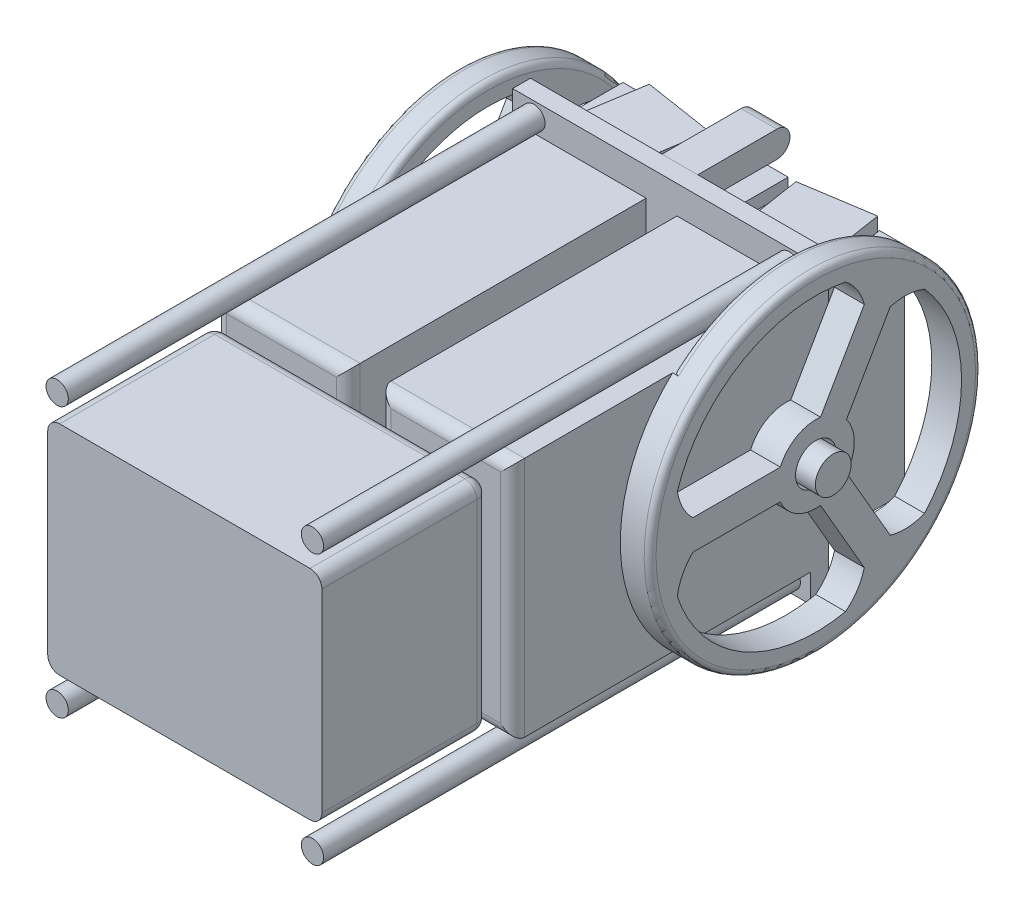
SolidWorks part; units mm, degrees
ref_plane "前视基准面" through (0, 0, 0) normal (0, 0, 1) x (1, 0, 0)
ref_plane "上视基准面" through (0, 0, 0) normal (0, 1, 0) x (1, 0, 0)
ref_plane "右视基准面" through (0, 0, 0) normal (1, 0, 0) x (0, 0, -1)
sketch "草图1" plane through (0, 0, 0) normal (0, 0, 1) x (1, 0, 0)
  line L1 (25, -25) -> (-25, -25)
  line L2 (25, -25) -> (25, 25)
  line L3 (25, 25) -> (-25, 25)
  line L4 (-25, -25) -> (-25, 25)
  line L5 (25, -25) -> (-25, 25) construction
  line L6 (25, 25) -> (-25, -25) construction
  point P0 (0, 0)
  dimension "D1" = 50
  dimension "D2" = 50
extrude "凸台-拉伸2" add sketch "草图1" along normal blind 3
sketch "草图3" plane through (0, 0, 3) normal (0, 0, 1) x (1, 0, 0)
  line L0 (-25, 25) -> (-25, -25) construction
  line L1 (-2.5874, 20.2707) -> (-25, 20.2707)
  line L2 (-2.5874, 20.2707) -> (-2.5874, -20.2707)
  line L3 (-2.5874, -20.2707) -> (-25, -20.2707)
  line L4 (-25, 20.2707) -> (-25, -20.2707)
  line L8 (2.5874, -20.2707) -> (25, -20.2707)
  line L9 (25, 20.2707) -> (25, -20.2707)
  line L10 (2.5874, 20.2707) -> (25, 20.2707)
  line L11 (2.5874, 20.2707) -> (2.5874, -20.2707)
  point P0 (-13.7937, 0)
extrude "凸台-拉伸10" add sketch "草图3" along normal blind 50 separate body
sketch "草图5" plane through (-25, 0, 0) normal (-1, 0, 0) x (0, 0, 1)
  circle A0 centre (7.1246, 0) radius 27.8036
  circle A1 centre (7.1246, 0) radius 3.407
extrude "凸台-拉伸13" add sketch "草图5" along normal blind 5
sketch "草图9" plane through (-25, 0, 0) normal (-1, 0, 0) x (0, 0, 1)
  circle A0 centre (7.1246, 0) radius 3
extrude "凸台-拉伸14" add sketch "草图9" along normal blind 8
mirror "镜向6" about plane through (0, 0, 0) normal (1, 0, 0) of "凸台-拉伸13"
sketch "草图10" plane through (25, 0, 0) normal (1, 0, 0) x (0, 0, -1)
  circle A0 centre (-7.1944, 0) radius 3.0039
extrude "凸台-拉伸15" add sketch "草图10" along normal blind 8
fillet "圆角1" radius 1 4 edges at (-30, 0, 34.9282) (-25, 0, -20.679) (25, 0, -20.679) (30, 0, 34.9282)
sketch "草图12" plane through (30, 0, 0) normal (1, 0, 0) x (0, 0, -1)
  line L0 (1.0139, 19.1245) -> (-6.3278, 6.4083)
  line L1 (-27.7561, 2.5141) -> (-13.0728, 2.5141)
  line L2 (-27.7561, -2.5141) -> (-13.0728, -2.5141)
  line L3 (5.3685, 16.6104) -> (-1.9732, 3.8942)
  line L4 (5.3685, -16.6104) -> (-1.9732, -3.8942)
  line L5 (1.0139, -19.1245) -> (-6.3278, -6.4083)
  arc A0 (-1.9732, -3.8942) -> (-1.9732, 3.8942) centre (-7.1246, 0) ccw
  arc A1 (11.1164, -16.2958) -> (11.1164, 16.2958) centre (-7.1246, 0) ccw
  arc A2 (-27.7561, -2.5141) -> (-30.3577, -7.6492) centre (-21.4669, -8.9269) ccw
  arc A3 (-27.7561, 2.5141) -> (-30.3577, 7.6492) centre (-21.4669, 8.9269) cw
  arc A4 (1.0139, 19.1245) -> (-2.1325, 23.945) centre (-7.6844, 16.8843) ccw
  arc A5 (5.3685, 16.6104) -> (11.1164, 16.2958) centre (7.7775, 7.9574) cw
  arc A6 (5.3685, -16.6104) -> (11.1164, -16.2958) centre (7.7775, -7.9574) ccw
  arc A7 (1.0139, -19.1245) -> (-2.1325, -23.945) centre (-7.6844, -16.8843) cw
  arc A8 (-13.0728, -2.5141) -> (-6.3278, -6.4083) centre (-7.1246, 0) ccw
  arc A9 (-30.3577, -7.6492) -> (-2.1325, -23.945) centre (-7.1246, 0) ccw
  arc A10 (-6.3278, 6.4083) -> (-13.0728, 2.5141) centre (-7.1246, 0) ccw
  arc A11 (-2.1325, 23.945) -> (-30.3577, 7.6492) centre (-7.1246, 0) ccw
  point P31 (-7.1246, 0)
  dimension "D1" = 3
extrude "切除-拉伸1" cut sketch "草图12" against normal blind 5
mirror "镜向7" about plane through (0, 0, 0) normal (1, 0, 0) of "切除-拉伸1"
fillet "圆角2" radius 2 8 edges at (13.7937, 20.2707, 53) (25, 0, 53) (13.7937, -20.2707, 53) (2.5874, 0, 53) (-2.5874, 0, 53) (-13.7937, 20.2707, 53) (-25, 0, 53) (-13.7937, -20.2707, 53)
sketch "草图13" plane through (0, 0, 3) normal (0, 0, 1) x (1, 0, 0)
  circle A0 centre (21.4182, 22.6266) radius 1.8728
  circle A1 centre (-21.4182, 22.6266) radius 1.8728
  circle A2 centre (-21.4182, -22.6266) radius 1.8728
  circle A3 centre (21.4182, -22.6266) radius 1.8728
extrude "凸台-拉伸16" add sketch "草图13" along normal blind 80
sketch "草图14" plane through (0, 0, 0) normal (0, 1, 0) x (1, 0, 0)
  line L0 (0, -8.552) -> (0, 2.2473) construction
  line L2 (-6, 12.2473) -> (6, 12.2473)
  line L3 (-6, 12.2473) -> (-6, 2.2473)
  line L4 (-6, 2.2473) -> (6, 2.2473)
  line L5 (6, 12.2473) -> (6, 2.2473)
  line L8 (7.303, 12.2473) -> (19.159, 14.1008)
  line L9 (7.303, 12.2473) -> (8.8476, 2.3673)
  line L10 (19.159, 14.1008) -> (20.7036, 4.2208)
  line L11 (8.8476, 2.3673) -> (20.7036, 4.2208)
  line L12 (-19.159, 14.1008) -> (-20.7036, 4.2208)
  line L13 (-8.8476, 2.3673) -> (-20.7036, 4.2208)
  line L14 (-7.303, 12.2473) -> (-8.8476, 2.3673)
  line L15 (-7.303, 12.2473) -> (-19.159, 14.1008)
  point P3 (0, 7.2473)
  dimension "D1" = 12
  dimension "D2" = 10
  dimension "D3" = 12
  dimension "D4" = 10
extrude "凸台-拉伸17" add sketch "草图14" along normal blind 20 and the other way blind 20 separate body
sketch "草图15" plane through (0, 0, 0) normal (0, 1, 0) x (1, 0, 0)
  line L0 (-25, 0) -> (25, 0) construction
  line L1 (-23.6334, 0) -> (23.6334, 0)
  line L2 (-23.6334, 0) -> (-23.6334, 2.066)
  line L3 (-6.1633, 2.066) -> (6.1633, 2.066)
  line L5 (-6.1633, 2.066) -> (-6.1633, 12.2452)
  line L6 (-6.1633, 12.2452) -> (-7.1581, 12.2452)
  line L7 (-7.1581, 12.2452) -> (-8.649, 2.066)
  line L8 (-8.649, 2.066) -> (-21.0986, 3.8893)
  line L9 (-21.0986, 3.8893) -> (-19.408, 14.1459)
  line L10 (-19.408, 14.1459) -> (-23.6334, 14.1459)
  line L11 (-23.6334, 14.1459) -> (-23.6334, 2.066)
  line L12 (6.1633, 2.066) -> (6.1633, 12.2452)
  line L13 (6.1633, 12.2452) -> (7.1581, 12.2452)
  line L14 (7.1581, 12.2452) -> (8.649, 2.066)
  line L15 (8.649, 2.066) -> (21.0986, 3.8893)
  line L16 (21.0986, 3.8893) -> (19.408, 14.1459)
  line L17 (19.408, 14.1459) -> (23.6334, 14.1459)
  line L18 (23.6334, 14.1459) -> (23.6334, 2.066)
  line L19 (23.6334, 0) -> (23.6334, 2.066)
extrude "凸台-拉伸18" add sketch "草图15" along normal blind 18 and the other way blind 18 separate body
sketch "草图16" plane through (0, 0, 83) normal (0, 0, 1) x (1, 0, 0)
  line L1 (23, -18.2707) -> (-23, -18.2707)
  line L2 (23, -18.2707) -> (23, 18.2707)
  line L3 (23, 18.2707) -> (-23, 18.2707)
  line L4 (-23, -18.2707) -> (-23, 18.2707)
  line L5 (23, -18.2707) -> (-23, 18.2707) construction
  line L6 (23, 18.2707) -> (-23, -18.2707) construction
  point P0 (0, 0)
extrude "凸台-拉伸19" add sketch "草图16" against normal blind 28 separate body
fillet "圆角3" radius 2 8 edges at (-23, 18.2707, 69) (23, 18.2707, 69) (23, 0, 55) (23, -18.2707, 69) (0, -18.2707, 55) (-23, -18.2707, 69) (-23, 0, 55) (0, 18.2707, 55)
sketch "草图17" plane through (0, 0, 0) normal (1, 0, 0) x (0, 0, -1)
  line L1 (0, 24.929) -> (13.3366, 24.929)
  line L2 (0, 24.929) -> (0, 20.5182)
  line L3 (0, 20.5182) -> (13.3366, 20.5182)
  line L4 (13.3366, 24.929) -> (13.3366, 20.5182)
  arc A0 (13.3366, 24.929) -> (13.3366, 20.5182) centre (13.3366, 22.7236) cw
extrude "凸台-拉伸20" add sketch "草图17" along normal blind 3 and the other way blind 3 contours A0 L4 | L4 L1 L2 L3 region at (0, 22.7236, -6.6683) region at (0, 22.7236, -14.2726)
mirror "镜向10" about plane through (0, 0, 0) normal (0, 1, 0) of "凸台-拉伸20"
